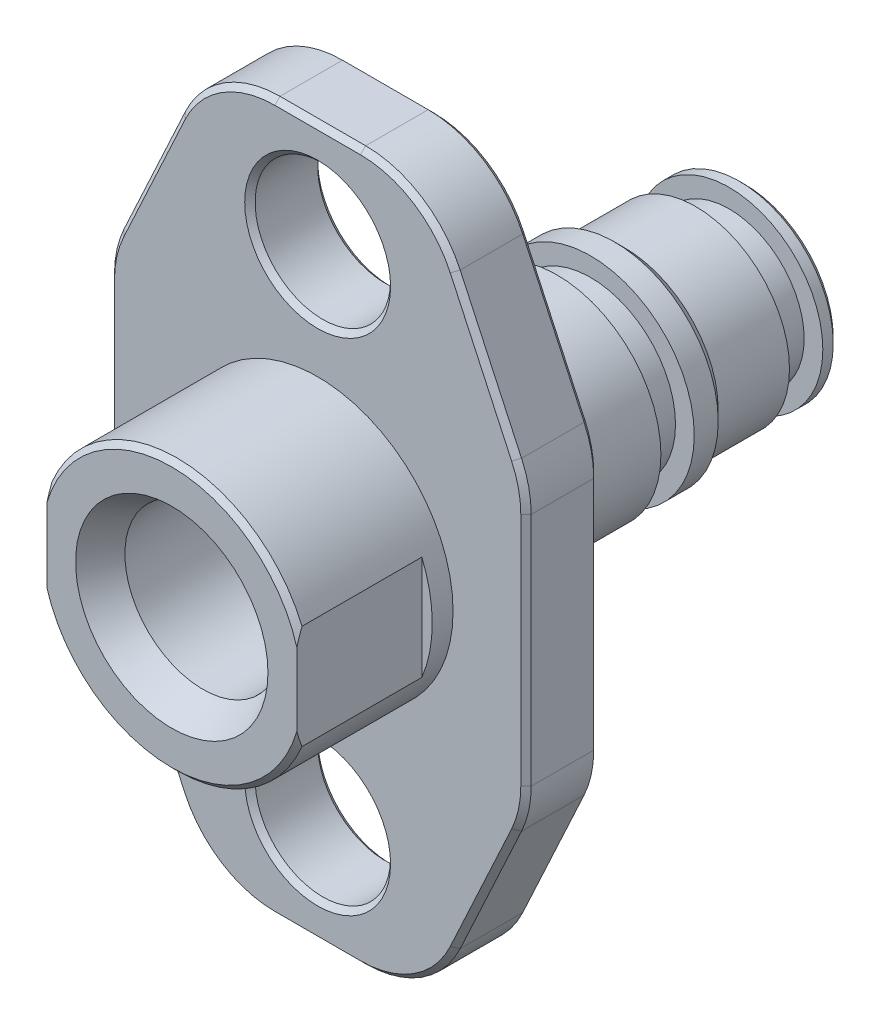
SolidWorks part; units mm, degrees
other "Markup1"
sketch "Sketch6" plane through (-20, -34, 0) normal (0, 0, 1) x (1, 0, 0)
material "316 S/Steel"
ref_plane "Front" through (0, 0, 0) normal (0, 0, 1) x (1, 0, 0)
ref_plane "Top" through (0, 0, 0) normal (0, 1, 0) x (1, 0, 0)
ref_plane "Right" through (0, 0, 0) normal (1, 0, 0) x (0, 0, -1)
sketch "Sketch1" plane through (0, 0, 0) normal (1, 0, 0) x (0, 0, -1)
  line L0 (0, 0) -> (55, 0) construction
  line L1 (14, 35) -> (21, 35)
  line L2 (0, 12.5) -> (0, 9.2321)
  line L3 (55, 4.75) -> (55, 8.49)
  line L4 (14, 35) -> (14, 13)
  line L5 (21, 35) -> (21, 9.95)
  line L6 (0.5, 13) -> (14, 13)
  line L7 (0, 35) -> (55, 35) construction
  line L8 (21, 9.95) -> (37, 9.95)
  line L9 (0, 35) -> (0, 0) construction
  line L10 (14, 35) -> (14, 0) construction
  line L11 (0, 13) -> (55, 13) construction
  line L12 (37, 8.15) -> (37, 9.95)
  line L13 (0, 9.95) -> (55, 9.95) construction
  line L14 (21, 35) -> (21, 0) construction
  line L15 (40.2, 8.15) -> (40.2, 9.95)
  line L16 (37, 8.15) -> (40.2, 8.15)
  line L17 (43.46, 8.99) -> (50.3, 8.99)
  line L18 (0, 8.15) -> (55, 8.15) construction
  line L19 (37, 0) -> (37, 9.95) construction
  line L20 (42.5, 9.95) -> (43.46, 8.99)
  line L21 (0, 8.99) -> (55, 8.99) construction
  line L22 (40.2, 9.95) -> (42.5, 9.95)
  line L23 (50.3, 7.2) -> (53.5, 7.2)
  line L24 (40.2, 0) -> (40.2, 9.95) construction
  line L25 (50.3, 7.2) -> (50.3, 8.99)
  line L26 (53.5, 7.2) -> (53.5, 8.99)
  line L27 (53.5, 8.99) -> (54.5, 8.99)
  line L28 (0, 7.2) -> (55, 7.2) construction
  line L29 (53.5, 0) -> (53.5, 9.95) construction
  line L30 (50.3, 0) -> (50.3, 9.95) construction
  line L31 (0, 12.5) -> (0.5, 13)
  line L32 (55, 0) -> (55, 9.95) construction
  line L33 (55, 8.49) -> (54.5, 8.99)
  line L34 (18.6524, 4.75) -> (55, 4.75)
  line L35 (17, 7.5) -> (18.6524, 4.75)
  line L36 (3, 7.5) -> (17, 7.5)
  line L37 (0, 4.75) -> (55, 4.75) construction
  line L38 (0, 9.2321) -> (3, 7.5)
  line L40 (0, 7.5) -> (55, 7.5) construction
  point P43 (17, 11.75)
  point P44 (17, 0)
  dimension "D1" = 55
  dimension "D2" = 35
  dimension "D3" = 14
  dimension "D4" = 7
  dimension "D5" = 34
  dimension "D6" = 13
  dimension "D7" = 9.95
  dimension "D8" = 12.5
  dimension "D9" = 45
  dimension "D10" = 8.15
  dimension "D11" = 18
  dimension "D12" = 3.2
  dimension "D13" = 8.99
  dimension "D14" = 1.5
  dimension "D15" = 3.2
  dimension "D16" = 7.2
  dimension "D17" = 0.5
  dimension "D18" = 45
  dimension "D19" = 45
  dimension "D20" = 0.5
  dimension "D21" = 17
  dimension "D22" = 7.5
  dimension "D23" = 4.75
  dimension "D24" = 59
  dimension "D25" = 30
  dimension "D26" = 3
revolve "Revolve1" add sketch "Sketch1" angle 360 about L0
cosmetic thread "Cosmetic Thread1" parameters "D2"=19.05
sketch "Sketch2" plane through (0, 0, 0) normal (0, 0, 1) x (1, 0, 0)
  line L0 (0, 0) -> (0, 34) construction
  line L1 (0, 0) -> (20, 0) construction
  line L2 (-4.1126, 34) -> (4.1126, 34)
  line L3 (20, -11.2955) -> (20, 11.2955)
  line L4 (19.0731, 15.5001) -> (13.1857, 28.2046)
  line L5 (19.0731, -15.5001) -> (13.1857, -28.2046)
  line L6 (0, 34) -> (20, 34) construction
  line L7 (20, 0) -> (20, 34) construction
  line L8 (-4.1126, -34) -> (4.1126, -34)
  line L9 (-19.0731, -15.5001) -> (-13.1857, -28.2046)
  line L10 (-19.0731, 15.5001) -> (-13.1857, 28.2046)
  line L11 (-20, -11.2955) -> (-20, 11.2955)
  arc A0 (19.0731, 15.5001) -> (20, 11.2955) centre (10, 11.2955) cw
  arc A1 (13.1857, 28.2046) -> (4.1126, 34) centre (4.1126, 24) ccw
  arc A2 (19.0731, -15.5001) -> (20, -11.2955) centre (10, -11.2955) ccw
  arc A3 (13.1857, -28.2046) -> (4.1126, -34) centre (4.1126, -24) cw
  arc A4 (-13.1857, -28.2046) -> (-4.1126, -34) centre (-4.1126, -24) ccw
  arc A5 (-19.0731, -15.5001) -> (-20, -11.2955) centre (-10, -11.2955) cw
  arc A6 (-13.1857, 28.2046) -> (-4.1126, 34) centre (-4.1126, 24) cw
  arc A7 (-19.0731, 15.5001) -> (-20, 11.2955) centre (-10, 11.2955) ccw
  circle A8 centre (0, 24) radius 6.5
  circle A9 centre (0, -24) radius 6.5
  point P9 (20, 13.5)
  point P12 (10.5, 34)
  point P19 (-10.5, 34)
  point P32 (0, -34)
  point P33 (-20, 13.5)
  dimension "D5" = 10
  dimension "D6" = 13
  dimension "D1" = 34
  dimension "D2" = 20
  dimension "D3" = 13.5
  dimension "D4" = 10.5
  dimension "D7" = 24
extrude "Cut-Extrude1" cut sketch "Sketch2" against normal blind 21 flip side to cut
sketch "Sketch5" plane through (0, 0, 0) normal (0, 0, 1) x (1, 0, 0)
  line L0 (0, 0) -> (-12, 0) construction
  line L2 (-12, 8.8472) -> (-14.0915, 8.8472)
  line L3 (-14.0915, 8.8472) -> (-14.0915, -9.1528)
  line L4 (-14.0915, -9.1528) -> (-12, -9.1528)
  line L6 (-12, 8.8472) -> (-12, -9.1528)
  dimension "D1" = 12
  dimension "D2" = 18
  dimension "D3" = 2.0915
extrude "Cut-Extrude2" cut sketch "Sketch5" against normal blind 12
pattern_circular "CirPattern1" count 2 over 180 about axis through (0, 0, 0) along (0, 0, 1) of "Cut-Extrude2" reverse direction yes
chamfer "Chamfer1" distance 0.5 angle 45 36 edges at (-6.5, -24, -14) (-6.5, -24, -21) (-6.5, 24, -14) (6.5, 24, -21) (9.4956, -32.4275, -14) (0, -34, -14) (16.1294, -21.8524, -14) (-9.4956, -32.4275, -14) (19.7655, -13.4483, -14) (-16.1294, -21.8524, -14) (20, 0, -14) (-19.7655, -13.4483, -14) (19.7655, 13.4483, -14) (-20, 0, -14) (16.1294, 21.8524, -14) (-19.7655, 13.4483, -14) (9.4956, 32.4275, -14) (-16.1294, 21.8524, -14) (0, 34, -14) (-9.4956, 32.4275, -14) (-9.4956, -32.4275, -21) (0, -34, -21) (-16.1294, -21.8524, -21) (9.4956, -32.4275, -21) (-19.7655, -13.4483, -21) (16.1294, -21.8524, -21) (-20, 0, -21) (19.7655, -13.4483, -21) (-19.7655, 13.4483, -21) (20, 0, -21) (-16.1294, 21.8524, -21) (19.7655, 13.4483, -21) (-9.4956, 32.4275, -21) (16.1294, 21.8524, -21) (0, 34, -21) (9.4956, 32.4275, -21)
